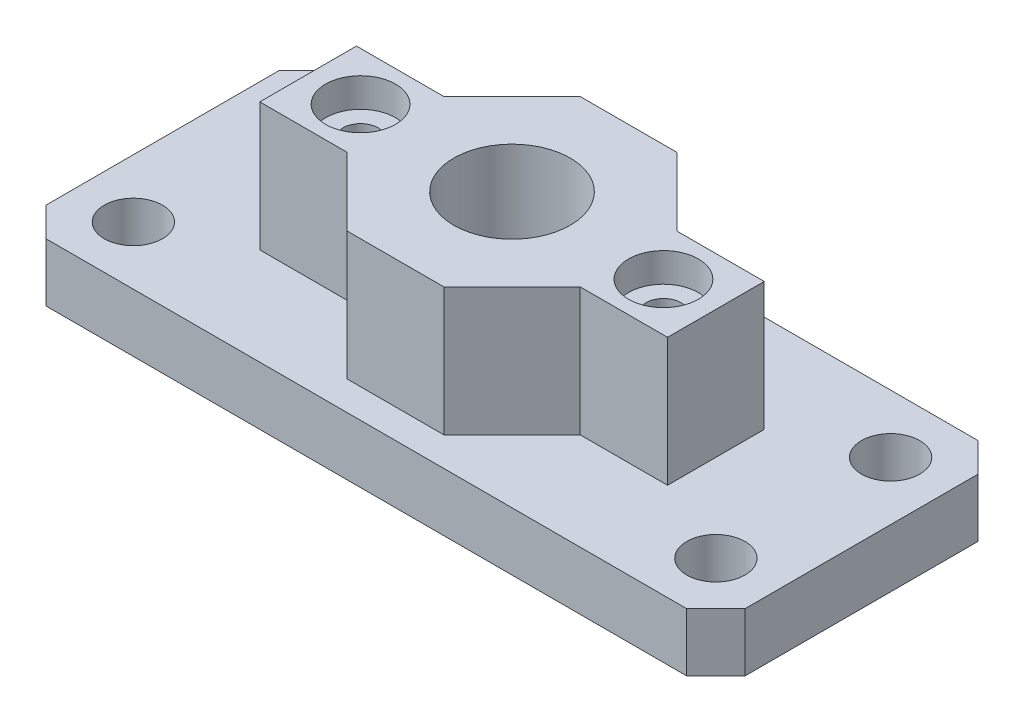
SolidWorks part; units mm, degrees
ref_plane "Front Plane" through (0, 0, 0) normal (0, 0, 1) x (1, 0, 0)
ref_plane "Top Plane" through (0, 0, 0) normal (0, 1, 0) x (1, 0, 0)
ref_plane "Right Plane" through (0, 0, 0) normal (1, 0, 0) x (0, 0, -1)
sketch "Sketch1" plane through (0, 0, 0) normal (0, 1, 0) x (1, 0, 0)
  line L0 (-35, -8.3) -> (-35, 8.3)
  line L1 (-60, 25) -> (60, 25)
  line L2 (-60, 25) -> (-60, -25)
  line L3 (-60, -25) -> (60, -25)
  line L4 (60, 25) -> (60, -25)
  line L5 (-60, 25) -> (60, -25) construction
  line L6 (-60, -25) -> (60, 25) construction
  line L7 (-35, 8.3) -> (-20, 8.3)
  line L8 (-20, 8.3) -> (-8.3, 20)
  line L9 (-8.3, 20) -> (8.3, 20)
  line L10 (8.3, 20) -> (20, 8.3)
  line L11 (20, 8.3) -> (35, 8.3)
  line L12 (35, 8.3) -> (35, -8.3)
  line L13 (35, -8.3) -> (20, -8.3)
  line L14 (20, -8.3) -> (8.3, -20)
  line L15 (8.3, -20) -> (-8.3, -20)
  line L16 (-8.3, -20) -> (-20, -8.3)
  line L17 (-20, -8.3) -> (-35, -8.3)
  line L18 (-1026, 0) -> (48974, 0) construction
  line L19 (0, -1000) -> (0, 49000) construction
  circle A0 centre (0, 0) radius 10
  circle A1 centre (-26, 0) radius 3
  circle A2 centre (-26, 0) radius 6
  circle A3 centre (26, 0) radius 3
  circle A4 centre (26, 0) radius 6
  circle A5 centre (50, 15) radius 5
  circle A6 centre (50, -15) radius 5
  circle A7 centre (-50, -15) radius 5
  circle A8 centre (-50, 15) radius 5
  point P0 (0, 0)
  dimension "D3" = 20
  dimension "D4" = 6
  dimension "D5" = 12
  dimension "D6" = 26
  dimension "D7" = 26
  dimension "D22" = 10
  dimension "D1" = 120
  dimension "D2" = 50
  dimension "D8" = 11.7
  dimension "D9" = 11.7
  dimension "D10" = 15
  dimension "D11" = 16.6
  dimension "D12" = 11.7
  dimension "D13" = 16.6
  dimension "D14" = 15
  dimension "D15" = 15
  dimension "D16" = 11.7
  dimension "D17" = 11.7
  dimension "D18" = 11.7
  dimension "D19" = 15
  dimension "D20" = 25
  dimension "D21" = 8.3
  dimension "D23" = 10
  dimension "D24" = 10
extrude "Boss-Extrude4" add sketch "Sketch1" along normal blind 10 contours L4 L1 L2 L3 A6 A5 L16 L17 L0 L7 L8 L9 L10 L11 L12 L13 L14 L15 A7 A8 region at (0, 0, -23.7)
extrude "Boss-Extrude5" add sketch "Sketch1<6>" along normal blind 32 contours L17 L16 L15 L14 L13 L12 L11 L10 L9 L8 L7 L0 A4 A2 A0 | A2 A1 | A1 | A4 A3 | A3 region at (-34.1938, 0, 0) region at (-26, 0, 0) region at (-31.8303, 0, 0) region at (26, 0, 0) region at (20.1697, 0, 0)
sketch "Sketch1<6>" plane through (0, 0, 0) normal (0, 1, 0) x (1, 0, 0) same geometry as "Sketch1"
extrude "Cut-Extrude1" cut sketch "Sketch1<9>" along normal blind 32 from offset 2 contours A1 | A3 region at (-26, 0, 0)
sketch "Sketch1<9>" plane through (0, 0, 0) normal (0, 1, 0) x (1, 0, 0) same geometry as "Sketch1"
extrude "Cut-Extrude2" cut sketch "Sketch1<10>" against normal blind 5 from surface contours A4 | A2 starting at face at (-26, 32, 3)
sketch "Sketch1<10>" plane through (0, 0, 0) normal (0, 1, 0) x (1, 0, 0) same geometry as "Sketch1"
chamfer "Chamfer1" distance 5 angle 45 4 edges at (60, 5, 25) (60, 5, -25) (-60, 5, -25) (-60, 5, 25)
